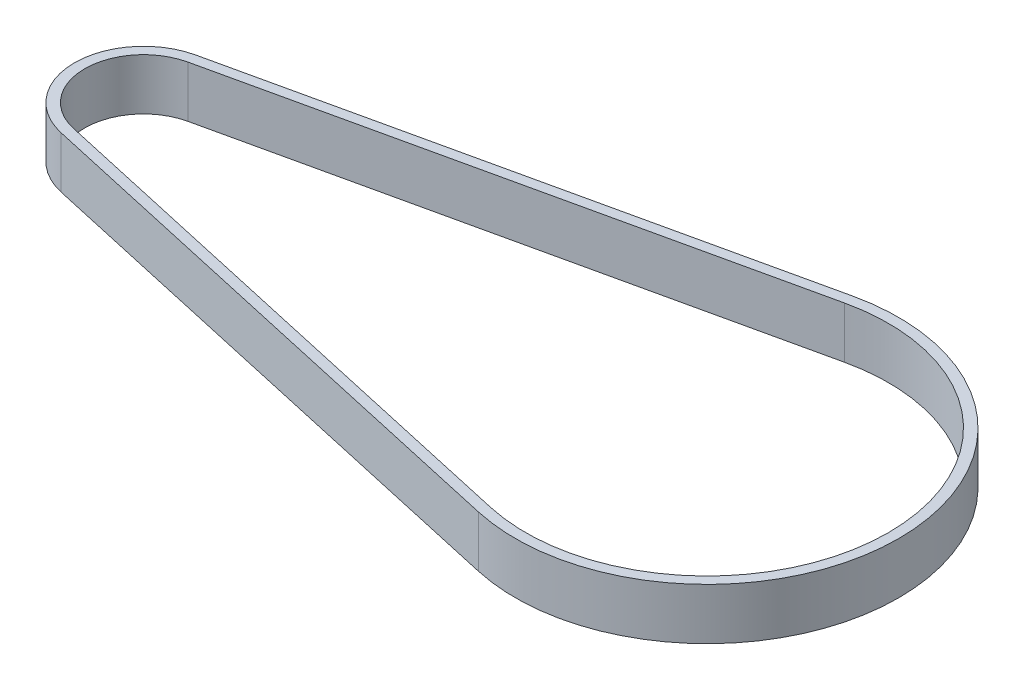
SolidWorks part; units mm, degrees
ref_plane "Ebene vorne" through (0, 0, 0) normal (0, 0, 1) x (1, 0, 0)
ref_plane "Ebene oben" through (0, 0, 0) normal (0, 1, 0) x (1, 0, 0)
ref_plane "Ebene rechts" through (0, 0, 0) normal (1, 0, 0) x (0, 0, -1)
sketch "Skizze1" plane through (0, 0, 0) normal (0, 1, 0) x (1, 0, 0)
  line L0 (-1.0388, 4.6606) -> (40.7837, 13.9819)
  line L1 (-12.3148, 0) -> (45.0363, 0) construction
  line L2 (0, 14.3488) -> (0, -8.3794) construction
  line L3 (-1.0388, -4.6606) -> (40.7837, -13.9819)
  arc A0 (-1.0388, 4.6606) -> (-1.0388, -4.6606) centre (0, 0) ccw
  arc A1 (40.7837, -13.9819) -> (40.7837, 13.9819) centre (43.9, 0) ccw
  dimension "D1" = 9.55
  dimension "D2" = 28.65
  dimension "D3" = 43.9
extrude "Linear-Austragen-Dünn1" add sketch "Skizze1" along normal blind 2 and the other way blind 2 thin thin type two direction wall 0.6 second wall 0.2
ref_axis "Achse1" through (0, -2.2, 0) along (0, 1, 0)
ref_axis "Achse2" through (43.9, -2, 0) along (0, 1, 0)
ref_plane "Ebene1" through (-0.9952, 2, 4.4654) normal (0.9761, 0, 0.2175) x (0.2175, 0, -0.9761)
